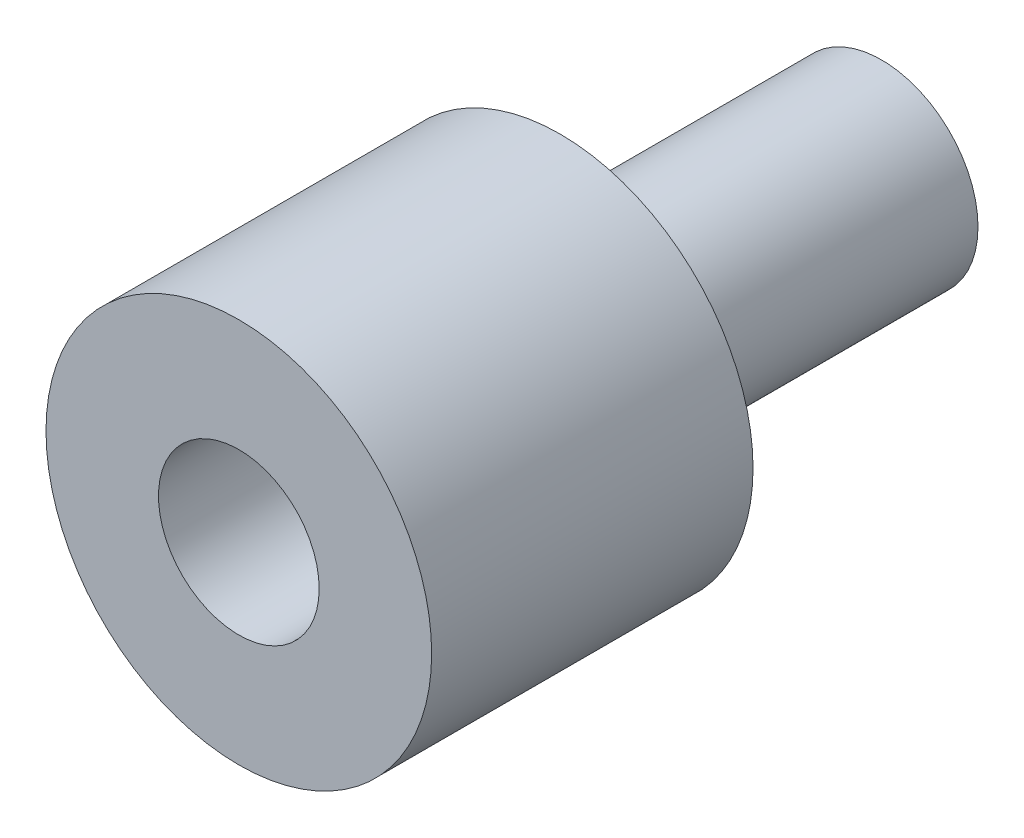
SolidWorks part; units mm, degrees
ref_plane "Front Plane" through (0, 0, 0) normal (0, 0, 1) x (1, 0, 0)
ref_plane "Top Plane" through (0, 0, 0) normal (0, 1, 0) x (1, 0, 0)
ref_plane "Right Plane" through (0, 0, 0) normal (1, 0, 0) x (0, 0, -1)
sketch "Sketch1" plane through (0, 0, 0) normal (0, 0, 1) x (1, 0, 0)
  circle A0 centre (0, 0) radius 12
  circle A1 centre (0, 0) radius 6
  dimension "D1" = 24
  dimension "D2" = 12
extrude "Boss-Extrude1" add sketch "Sketch1" along normal blind 20 contours A0
extrude "Boss-Extrude2" add sketch "Sketch1<4>" against normal blind 20 contours A1
sketch "Sketch1<4>" plane through (0, 0, 0) normal (0, 0, 1) x (1, 0, 0) same geometry as "Sketch1"
sketch "Sketch2" plane through (0, 0, 20) normal (0, 0, 1) x (1, 0, 0)
  circle A0 centre (0, 0) radius 5
  dimension "D1" = 10
extrude "Cut-Extrude1" cut sketch "Sketch2" against normal blind 12
